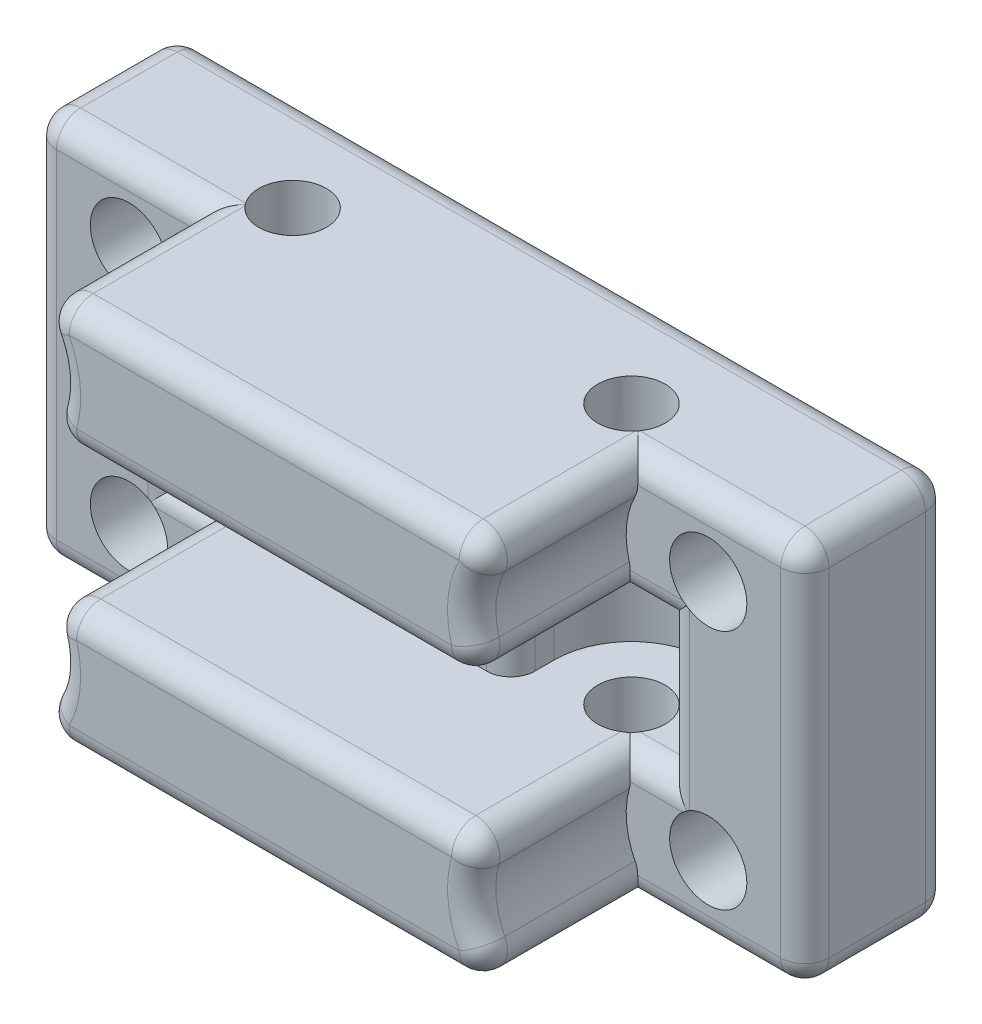
SolidWorks part; units mm, degrees
ref_plane "Front Plane" through (0, 0, 0) normal (0, 0, 1) x (1, 0, 0)
ref_plane "Top Plane" through (0, 0, 0) normal (0, 1, 0) x (1, 0, 0)
ref_plane "Right Plane" through (0, 0, 0) normal (1, 0, 0) x (0, 0, -1)
sketch "Sketch1" plane through (0, 0, 0) normal (0, 0, 1) x (1, 0, 0)
  line L0 (-25.4, 12.7) -> (25.4, -12.7) construction
  line L1 (-25.4, -12.7) -> (25.4, -12.7)
  line L2 (-25.4, -12.7) -> (-25.4, 12.7)
  line L3 (-25.4, 12.7) -> (25.4, 12.7)
  line L4 (25.4, -12.7) -> (25.4, 12.7)
  point P6 (0, 0)
  dimension "D1" = 50.8
  dimension "D2" = 25.4
extrude "Boss-Extrude1" add sketch "Sketch1" along normal mid plane 9.525
sketch "Sketch2" plane through (0, 0, 4.7625) normal (0, 0, 1) x (1, 0, 0)
  line L0 (-25.4, -12.7) -> (25.4, -12.7) construction
  line L1 (-25.4, 12.7) -> (-25.4, -12.7) construction
  circle A0 centre (-19.05, 7.9375) radius 2.54
  dimension "D1" = 5.08
  dimension "D2" = 20.6375
  dimension "D3" = 6.35
extrude "Cut-Extrude1" cut sketch "Sketch2" against normal through all
sketch "Sketch4" plane through (0, 0, 0) normal (0, 1, 0) x (1, 0, 0)
  line L7 (25.4, -4.7625) -> (-25.4, -4.7625) construction
  line L8 (-16.2242, -1.905) -> (-16.2243, -4.7625)
  line L9 (-6.0642, -1.905) -> (-6.0643, -4.7625)
  line L10 (-6.0643, -4.7625) -> (-16.2243, -4.7625)
  line L11 (-25.4, -4.7625) -> (-25.4, 4.7625) construction
  arc A2 (-6.0642, -1.905) -> (-16.2242, -1.905) centre (-11.1442, -1.905) ccw
  dimension "D1" = 10.16
  dimension "D2" = 2.8575
  dimension "D3" = 14.2558
extrude "Cut-Extrude2" cut sketch "Sketch4" against normal mid plane 8.89
sketch "Sketch5" plane through (0, 12.7, 0) normal (0, 1, 0) x (1, 0, 0)
  line L0 (25.4, -4.7625) -> (-25.4, -4.7625) construction
  line L1 (-25.4, -4.7625) -> (-25.4, 4.7625) construction
  circle A0 centre (-11.1442, -1.905) radius 2.2225
  dimension "D3" = 4.445
  dimension "D1" = 2.8575
  dimension "D2" = 14.2558
extrude "Cut-Extrude3" cut sketch "Sketch5" against normal through all
sketch "Sketch6" plane through (0, 0, 4.7625) normal (0, 0, 1) x (1, 0, 0)
  line L0 (-16.51, 12.7) -> (16.51, 12.7)
  line L2 (-14.9347, 4.445) -> (14.9347, 4.445)
  line L3 (-16.2242, 4.445) -> (-6.0642, 4.445) construction
  line L4 (25.4, 12.7) -> (-25.4, 12.7) construction
  arc A0 (-14.9347, 4.445) -> (-16.51, 12.7) centre (-19.05, 7.9375) ccw
  arc A1 (16.51, 12.7) -> (14.9347, 4.445) centre (19.05, 7.9375) ccw
  point P1 (-16.51, 12.7)
  point P4 (-16.446, 12.7)
  point P9 (16.3649, 12.7)
  point P14 (16.51, 12.7)
  dimension "D1" = 10.795
  dimension "D2" = 38.1
  dimension "D3" = 29.8695
extrude "Boss-Extrude2" add sketch "Sketch6" along normal blind 10.16
mirror "Mirror5" about plane through (0, 0, 0) normal (1, 0, 0) of "Cut-Extrude3", "Cut-Extrude2", "Cut-Extrude1"
mirror "Mirror6" about plane through (0, 0, 0) normal (0, 1, 0) of "Boss-Extrude2", "Mirror5"
fillet "Fillet1" radius 1.5875 38 edges at (25.4, -12.7, 0) (25.4, 0, 4.7625) (25.4, 12.7, 0) (25.4, 0, -4.7625) (-25.4, 12.7, 0) (-25.4, 0, 4.7625) (-25.4, -12.7, 0) (-25.4, 0, -4.7625) (20.955, 12.7, 4.7625) (20.955, -12.7, 4.7625) (0, 12.7, -4.7625) (0, -12.7, -4.7625) (6.0642, 0, 4.7625) (14.9347, 4.445, 9.8425) (15.5795, 4.445, 4.7625) (16.2243, 0, 4.7625) (15.5795, -4.445, 4.7625) (14.9347, -4.445, 9.8425) (13.7482, -8.9492, 14.9225) (0, -4.445, 14.9225) (0, -12.7, 14.9225) (-20.955, -12.7, 4.7625) (-16.51, -12.7, 9.8425) (-13.7482, -8.9492, 14.9225) (-14.9347, -4.445, 9.8425) (-15.5795, -4.445, 4.7625) (-6.0642, 0, 4.7625) (-16.2243, 0, 4.7625) (-15.5795, 4.445, 4.7625) (-14.9347, 4.445, 9.8425) (-20.955, 12.7, 4.7625) (-16.51, 12.7, 9.8425) (13.7482, 8.9492, 14.9225) (0, 4.445, 14.9225) (-13.7482, 8.9492, 14.9225) (0, 12.7, 14.9225) (16.51, -12.7, 9.8425) (16.51, 12.7, 9.8425)
